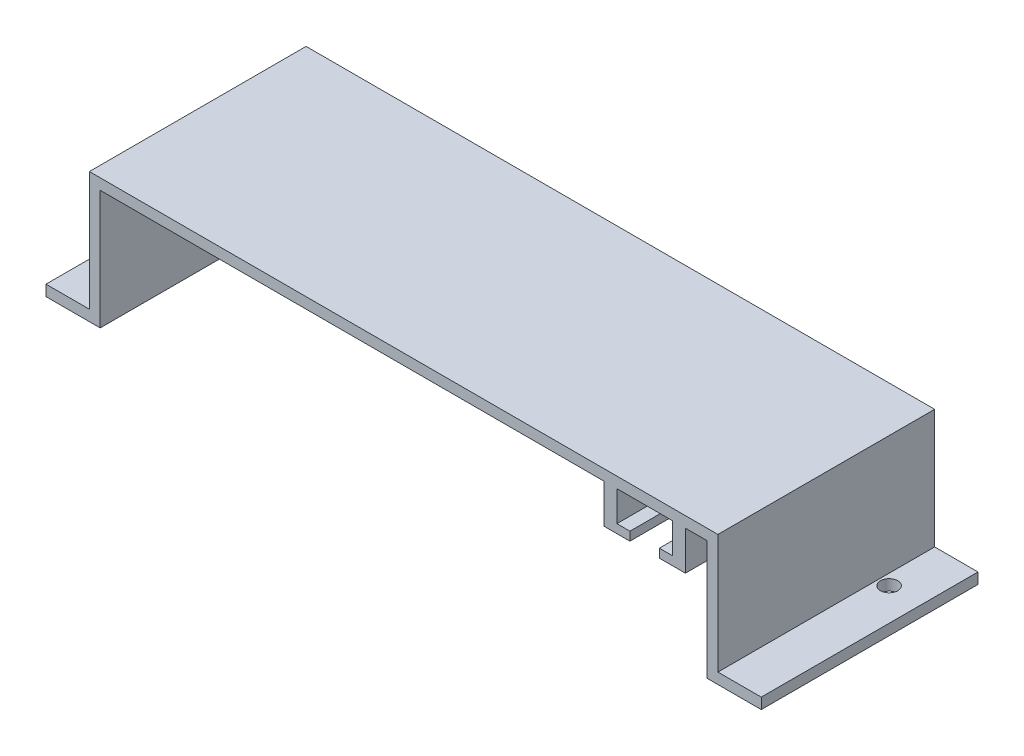
SolidWorks part; units mm, degrees
ref_plane "Front Plane" through (0, 0, 0) normal (0, 0, 1) x (1, 0, 0)
ref_plane "Top Plane" through (0, 0, 0) normal (0, 1, 0) x (1, 0, 0)
ref_plane "Right Plane" through (0, 0, 0) normal (1, 0, 0) x (0, 0, -1)
sketch "Sketch1" plane through (0, 0, 0) normal (0, 1, 0) x (1, 0, 0)
  line L1 (-88.9, 31.75) -> (88.9, 31.75)
  line L2 (-88.9, 31.75) -> (-88.9, -31.75)
  line L3 (-88.9, -31.75) -> (88.9, -31.75)
  line L4 (88.9, 31.75) -> (88.9, -31.75)
  line L5 (-88.9, 31.75) -> (88.9, -31.75) construction
  line L6 (-88.9, -31.75) -> (88.9, 31.75) construction
  point P0 (0, 0)
  dimension "D1" = 177.8
  dimension "D2" = 63.5
extrude "Boss-Extrude1" add sketch "Sketch1" along normal blind 3.175
sketch "Sketch3" plane through (0, 3.175, 0) normal (0, 1, 0) x (1, 0, 0)
  line L0 (-88.9, -31.75) -> (88.9, -31.75) construction
  line L1 (-88.9, 31.75) -> (-92.075, 31.75)
  line L2 (-88.9, 31.75) -> (-88.9, -31.75)
  line L3 (-88.9, -31.75) -> (-92.075, -31.75)
  line L4 (-92.075, 31.75) -> (-92.075, -31.75)
  line L5 (0, -55) -> (0, 55) construction
  line L6 (88.9, -31.75) -> (92.075, -31.75)
  line L7 (92.075, 31.75) -> (92.075, -31.75)
  line L8 (88.9, 31.75) -> (92.075, 31.75)
  line L9 (88.9, 31.75) -> (88.9, -31.75)
  dimension "D1" = 3.175
extrude "Boss-Extrude2" add sketch "Sketch3" against normal blind 38.1
sketch "Sketch4" plane through (92.075, 0, 0) normal (1, 0, 0) x (0, 0, -1)
  line L0 (31.75, -34.925) -> (31.75, 3.175) construction
  line L1 (-31.75, -34.925) -> (31.75, -34.925)
  line L2 (-31.75, -34.925) -> (-31.75, -31.75)
  line L3 (-31.75, -31.75) -> (31.75, -31.75)
  line L4 (31.75, -34.925) -> (31.75, -31.75)
  dimension "D1" = 3.175
extrude "Boss-Extrude3" add sketch "Sketch4" along normal blind 12.7
sketch "Sketch5" plane through (0, -34.925, 0) normal (0, -1, 0) x (1, 0, 0)
  line L0 (88.9, -31.75) -> (88.9, 31.75) construction
  line L1 (104.775, -31.75) -> (88.9, -31.75) construction
  circle A0 centre (95.25, -15.24) radius 2.54
  dimension "D1" = 5.08
  dimension "D2" = 6.35
  dimension "D3" = 16.51
extrude "Cut-Extrude1" cut sketch "Sketch5" against normal blind 12.7
mirror "Mirror1" about plane through (0, 0, 0) normal (1, 0, 0) of "Boss-Extrude3", "Cut-Extrude1"
sketch "Sketch6" plane through (0, 0, 31.75) normal (0, 0, 1) x (1, 0, 0)
  line L0 (58.674, 0) -> (58.674, -11.43)
  line L1 (-88.9, 0) -> (88.9, 0) construction
  line L2 (58.674, -11.43) -> (66.294, -11.43)
  line L3 (66.294, -11.43) -> (66.294, -8.89)
  line L4 (66.294, -8.89) -> (62.484, -8.89)
  line L5 (62.484, -8.89) -> (62.484, 0)
  line L6 (82.55, 0) -> (82.55, -11.43)
  line L7 (82.55, -11.43) -> (74.93, -11.43)
  line L8 (74.93, -11.43) -> (74.93, -8.89)
  line L9 (74.93, -8.89) -> (78.74, -8.89)
  line L10 (78.74, -8.89) -> (78.74, 0)
  line L11 (-88.9, -34.925) -> (-88.9, 0) construction
  line L12 (82.55, 0) -> (78.74, 0)
  line L13 (62.484, 0) -> (58.674, 0)
  dimension "D1" = 11.43
  dimension "D2" = 2.54
  dimension "D3" = 3.81
  dimension "D4" = 3.81
  dimension "D5" = 167.64
  dimension "D6" = 16.256
extrude "Boss-Extrude4" add sketch "Sketch6" against normal up to surface (63.5 mm away) up to face at (0, -21.6958, -31.75)
